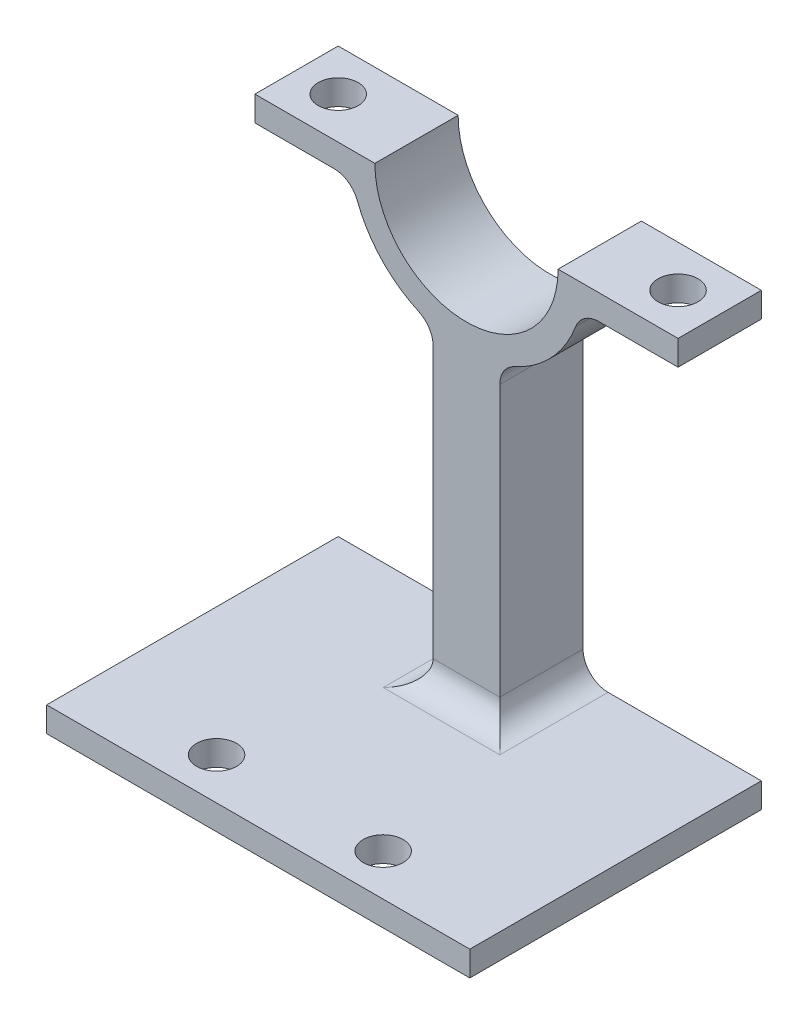
SolidWorks part; units mm, degrees
material "Windform GT"
ref_plane "Front Plane" through (0, 0, 0) normal (0, 0, 1) x (1, 0, 0)
ref_plane "Top Plane" through (0, 0, 0) normal (0, 1, 0) x (1, 0, 0)
ref_plane "Right Plane" through (0, 0, 0) normal (1, 0, 0) x (0, 0, -1)
sketch "Sketch1" plane through (0, 0, 0) normal (0, 0, 1) x (1, 0, 0)
  line L0 (5.5, 0) -> (12.7, 0)
  line L1 (12.7, 0) -> (12.7, -1.5)
  line L2 (12.7, -1.5) -> (6.8374, -1.5)
  line L5 (0, 0) -> (0, -7) construction
  line L7 (-12.7, -1.5) -> (-6.8374, -1.5)
  line L8 (-12.7, 0) -> (-12.7, -1.5)
  line L9 (-5.5, 0) -> (-12.7, 0)
  arc A2 (5.5, 0) -> (-5.5, 0) centre (0, 0) cw
  arc A3 (-6.8374, -1.5) -> (6.8374, -1.5) centre (0, 0) ccw
  dimension "D1" = 7
  dimension "D2" = 5.5
  dimension "D3" = 12.7
  dimension "D4" = 1.5
extrude "Boss-Extrude1" add sketch "Sketch1" along normal mid plane 5
sketch "Sketch2" plane through (0, 0, 0) normal (0, 1, 0) x (1, 0, 0)
  line L0 (12.7, 0) -> (-12.7, 0) construction
  line L1 (-12.7, -2.5) -> (-12.7, 2.5) construction
  line L2 (0, 0) -> (0, 2.5) construction
  line L3 (5.5, 2.5) -> (-5.5, 2.5) construction
  circle A0 centre (-10.2, 0) radius 1.2
  circle A1 centre (10.2, 0) radius 1.2
  dimension "D1" = 2.5
  dimension "D2" = 2.4
extrude "Cut-Extrude1" cut sketch "Sketch2" against normal through all
sketch "Sketch6" plane through (0, 0, 0) normal (0, 1, 0) x (1, 0, 0)
  line L0 (-5.5, -2.5) -> (-5.5, 2.5) construction
  line L1 (2, 2.5) -> (-2, 2.5)
  line L2 (2, 2.5) -> (2, -2.5)
  line L3 (2, -2.5) -> (-2, -2.5)
  line L4 (-2, 2.5) -> (-2, -2.5)
  line L5 (2, 2.5) -> (-2, -2.5) construction
  line L6 (2, -2.5) -> (-2, 2.5) construction
  point P0 (0, 0)
  dimension "D1" = 4
extrude "Boss-Extrude2" add sketch "Sketch6" along normal up to surface (18.7918 mm away) from offset 25.5 up to face at (0, -4.25, 0) offset against normal yes
sketch "Sketch7" plane through (0, -25.5, 0) normal (0, -1, 0) x (1, 0, 0)
  line L0 (0, 0) -> (0, 15) construction
  line L5 (12.7, 2.5) -> (12.7, -2.5) construction
  line L7 (5.5, 2.5) -> (-5.5, 2.5) construction
  line L13 (0, 0) -> (0, -2.5) construction
  line L18 (2, -2.5) -> (-2, -2.5) construction
  line L19 (12.7, -2.5) -> (-12.7, -2.5)
  line L20 (-6.8374, -2.5) -> (-2, -2.5) construction
  line L29 (-12.7, -2.5) -> (-12.7, 15)
  line L30 (-12.7, 15) -> (12.7, 15)
  line L31 (12.7, -2.5) -> (12.7, 15)
  point P2 (0, 0)
  point P5 (11.8083, -2.5)
  point P7 (-12.7, 2.5)
  point P8 (-12.8557, -1.7726)
  point P20 (-12.7, -2.5)
  point P21 (12.3721, -2.5)
  dimension "D1" = 12.5
extrude "Boss-Extrude4" add sketch "Sketch7" along normal blind 1.5
fillet "Fillet1" radius 1.5 7 edges at (2, -25.5, 0) (-2, -25.5, 0) (-6.8374, -1.5, 0) (-2, -6.7082, 0) (2, -6.7082, 0) (6.8374, -1.5, 0) (0, -25.5, 2.5)
sketch "Sketch8" plane through (0, 0, 0) normal (0, 1, 0) x (1, 0, 0)
  line L0 (0, 2.5) -> (0, -15) construction
  line L1 (12.7, -15) -> (-12.7, -15) construction
  line L2 (-5, 2.5) -> (-5, -15) construction
  line L3 (5, 2.5) -> (5, -15) construction
  line L4 (5.5, 2.5) -> (-5.5, 2.5) construction
  line L5 (-5.5, 2.5) -> (-12.7, 2.5) construction
  circle A0 centre (-5, -12.5) radius 1.2
  circle A3 centre (5, -12.5) radius 1.2
  dimension "D2" = 2.4
  dimension "D1" = 2.5
  dimension "D4" = 5
extrude "Cut-Extrude3" cut sketch "Sketch8" against normal through all
